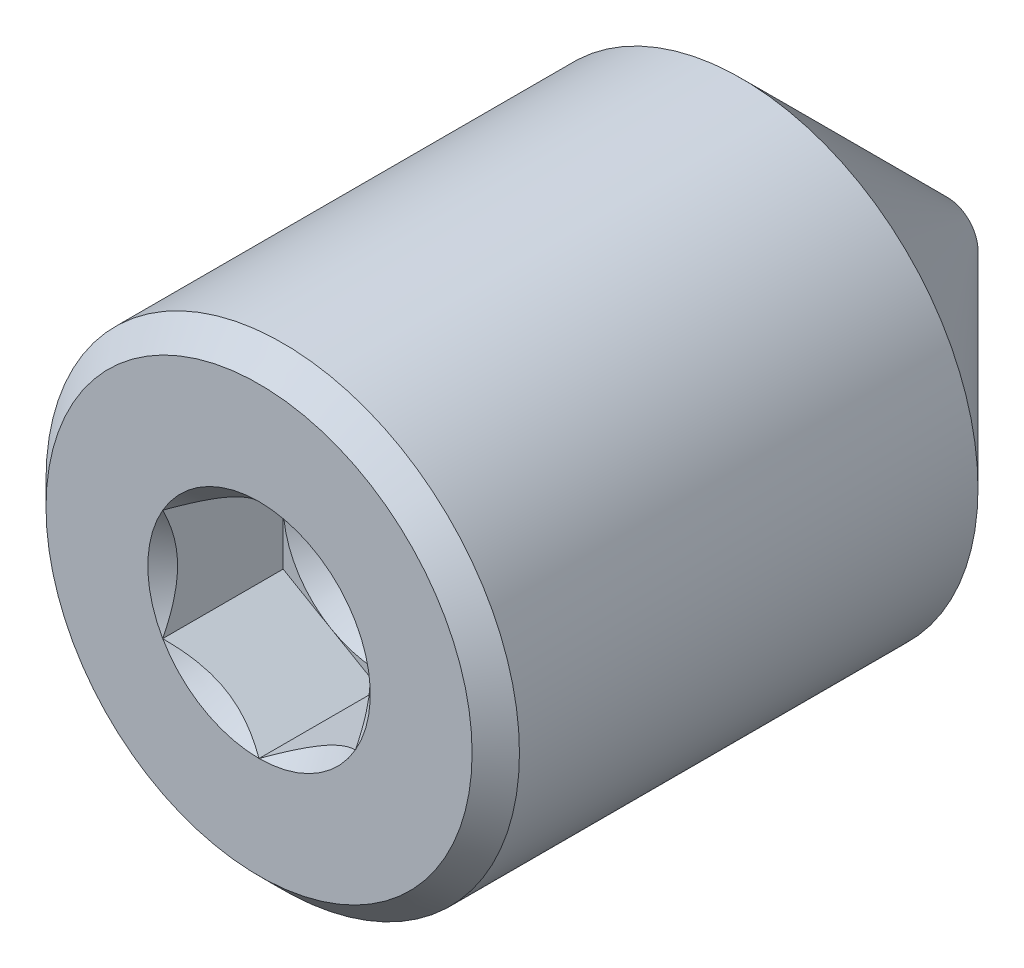
SolidWorks part; units mm, degrees
ref_plane "Front Plane" through (0, 0, 0) normal (0, 0, 1) x (1, 0, 0)
ref_plane "Top Plane" through (0, 0, 0) normal (0, 1, 0) x (1, 0, 0)
ref_plane "Right Plane" through (0, 0, 0) normal (1, 0, 0) x (0, 0, -1)
sketch "Sketch1" plane through (0, 0, 0) normal (1, 0, 0) x (0, 0, -1)
  line L0 (1.5592, 1.1412) -> (1.7857, 0.7489) construction
  line L1 (-1.5875, 1.0922) -> (1.5875, 1.0922) construction
  line L2 (-1.5875, 1.0922) -> (-1.5875, -1.0922) construction
  line L3 (-1.5875, -1.0922) -> (1.5875, -1.0922) construction
  line L4 (1.5875, 1.0922) -> (1.5875, -1.0922) construction
  line L5 (0, -1.0922) -> (0, 1.0922) construction
  line L6 (-1.5875, 0) -> (1.5875, 0) construction
  line L7 (1.7857, 0.7489) -> (2.0122, 1.1412) construction
  line L8 (2.0122, 1.1412) -> (1.5592, 1.1412) construction
  line L9 (1.7857, 1.1412) -> (1.7857, 1.0922) construction
  line L10 (1.7857, 1.0922) -> (1.7857, 0.798) construction
  line L11 (1.7857, 0.798) -> (1.7857, 0.7489) construction
  line L12 (1.7857, 1.1167) -> (1.998, 1.1167) construction
  line L13 (1.7857, 1.1167) -> (1.5733, 1.1167) construction
  line L14 (1.5875, 1.0922) -> (1.9839, 1.0922) construction
  line L15 (1.7574, 0.798) -> (1.814, 0.798) construction
  line L20 (1.5875, 0.142) -> (0.6373, 1.0922) construction
  line L21 (1.5875, 0.142) -> (1.4455, 0) construction
  line L22 (1.4455, 0) -> (1.5875, -0.142) construction
  line L23 (1.5875, -0.142) -> (0.6373, -1.0922) construction
  line L24 (0.6373, -1.0922) -> (0.6373, 1.0922) construction
  point P0 (0, 0)
  point P2 (2.4333, 0.7039)
  point P20 (1.5875, 0.142)
  point P21 (-1.5875, -0.4445)
  point P25 (1.357, -1.0922)
  point P26 (1.5875, -0.142)
  dimension "Length" = 3.175
  dimension "Screw Size Decimal Equivalent" = 2.1844
  dimension "Thread Pitch" = 0.453
  dimension "D2" = 0.0566
  dimension "Point" = 0.284
  dimension "Cone Point Angle" = 90
  dimension "Drive Size" = 0.889
  dimension "D3" = 90
  dimension "D1" = 2.9445
  dimension "D4" = 2.54
sketch "Sketch2" plane through (0, 0, 0) normal (1, 0, 0) x (0, 0, -1)
  line L0 (-1.5875, 0) -> (1.5875, 0)
  line L1 (1.5875, 0) -> (1.5875, 0.142)
  line L2 (1.5875, 0.142) -> (0.6373, 1.0922)
  line L3 (0.6373, 1.0922) -> (-1.5875, 1.0922)
  line L4 (-1.5875, 1.0922) -> (-1.5875, 0)
revolve "Revolve1" add sketch "Sketch2" angle 360 about L6
chamfer "Chamfer1" distance 0.1092 angle 45 1 edges at (1.0922, 0, 1.5875)
sketch "Sketch3" plane through (0, 0, 1.5875) normal (0, 0, 1) x (1, 0, 0)
  line L1 (0, -0.5133) -> (0.4445, -0.2566)
  line L2 (0.4445, -0.2566) -> (0.4445, 0.2566)
  line L3 (0.4445, 0.2566) -> (0, 0.5133)
  line L4 (0, 0.5133) -> (-0.4445, 0.2566)
  line L5 (-0.4445, 0.2566) -> (-0.4445, -0.2566)
  line L6 (-0.4445, -0.2566) -> (0, -0.5133)
  circle A0 centre (0, 0) radius 0.4445 construction
  dimension "D1" = 0.889
extrude "Cut-Extrude1" cut sketch "Sketch3" against normal blind 0.5556
sketch "Sketch4" plane through (0, 0, 1.5875) normal (0, 0, 1) x (1, 0, 0)
  circle A0 centre (0, 0) radius 0.5133
extrude "Cut-Extrude2" cut sketch "Sketch4" against normal through all draft 45
sketch "Sketch5" plane through (0, 0, 1.0319) normal (0, 0, 1) x (1, 0, 0)
  line L0 (0, 0.5133) -> (0.4445, 0.2566) construction
  circle A0 centre (0, 0) radius 0.4445
extrude "Cut-Extrude3" cut sketch "Sketch5" against normal through all draft 45
sketch "Sketch6" [suppressed] plane through (0, 0, -1.5875) normal (0, 0, -1) x (-1, 0, 0)
  circle A0 centre (0, 0) radius 1.0922 construction
  circle A1 centre (0, 0) radius 1.0922
curve "Helix/Spiral1" [suppressed] pitch 0.453 height 3.628 turns 8.0088
sketch "Sketch7" [suppressed] plane through (0, 0, 0) normal (1, 0, 0) x (0, 0, -1)
  line L0 (1.5733, 1.1167) -> (1.998, 1.1167)
  line L1 (1.998, 1.1167) -> (1.814, 0.798)
  line L2 (1.814, 0.798) -> (1.7574, 0.798)
  line L3 (1.7574, 0.798) -> (1.5733, 1.1167)
sweep "Cut-Sweep1" [suppressed] cut profiles "Sketch7" path "Helix/Spiral1"
equation "\"D2@Sketch1\" = \"Thread Pitch@Sketch1\" / 8"
equation "\"Point@Sketch1\"=\"Screw Size Decimal Equivalent@Sketch1\"*.13"
equation "\"D1@Chamfer1\"=\"Screw Size Decimal Equivalent@Sketch1\"*.05"
equation "\"D1@Sketch3\"=\"Drive Size@Sketch1\""
equation "\"D1@Cut-Extrude1\"=\"Drive Size@Sketch1\"*.625"
equation "\"D4@Helix/Spiral1\"=\"Thread Pitch@Sketch1\""
equation "\"D3@Helix/Spiral1\"=\"Length@Sketch1\"+\"Thread Pitch@Sketch1\""
equation "\"D3@Sketch1\"=\"Cone Point Angle@Sketch1\""
equation "\"D1@Sketch1\"=\"Thread Pitch@Sketch1\"*6.5"
